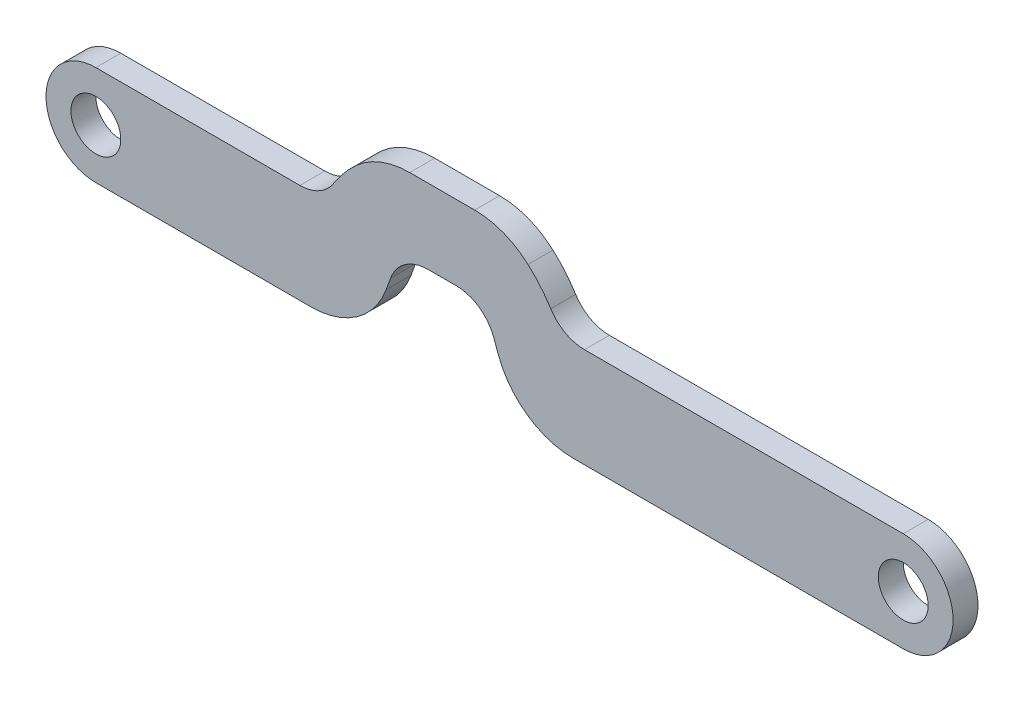
SolidWorks part; units mm, degrees
ref_plane "Спереди" through (0, 0, 0) normal (0, 0, 1) x (1, 0, 0)
ref_plane "Сверху" through (0, 0, 0) normal (0, 1, 0) x (1, 0, 0)
ref_plane "Справа" through (0, 0, 0) normal (1, 0, 0) x (0, 0, -1)
sketch "Эскиз1" plane through (0, 0, 0) normal (0, 0, 1) x (1, 0, 0)
  line L0 (0, 0) -> (-32.398, 0)
  line L1 (-32.398, -2) -> (0, -2)
  line L2 (-32.398, 2) -> (0, 2)
  circle A0 centre (-32.398, 0) radius 1
  circle A1 centre (0, 0) radius 1
  circle A2 centre (-32.398, 0) radius 2
  circle A3 centre (0, 0) radius 2
  dimension "D1" = 32.398
extrude "Бобышка-Вытянуть1" add sketch "Эскиз1" along normal mid plane 1 contours A3 L2 A2 L0 | A3 L0 A2 L1 | A2 A0 | A3 A1 region at (-16.199, 1.0162, 0) region at (-31.0238, -1.3742, 0) region at (-16.199, -1.0162, 0) region at (-1.3742, 1.3742, 0)
sketch "Sketch3" plane through (0, 0, 0) normal (0, 0, 1) x (1, 0, 0)
  line L0 (0, 0) -> (-18.5, 0)
  line L1 (-18.5, -2) -> (-13.3079, -2)
  line L2 (-20.5203, 0.7353) -> (-21.5159, -2)
  line L3 (-16.4797, 0.7353) -> (-15.4841, -2)
  line L4 (-18.5, 0) -> (-18.5, -2)
  line L5 (-18.5, -2) -> (-23.727, -2)
  line L6 (-23.3394, 1.7614) -> (-24.335, -0.9739)
  line L7 (-13.6606, 1.7614) -> (-12.665, -0.9739)
  line L8 (-18.5, 2.15) -> (-18.5, 1.65)
  line L9 (-18.5, 1.65) -> (-16.1863, 1.65)
  line L10 (-18.5, 1.65) -> (-20.9188, 1.65)
  line L11 (-18.5, 5.15) -> (-18.5, 4.65)
  line L12 (-18.5, 4.65) -> (-22.2565, 4.65)
  line L13 (-18.5, 4.65) -> (-15.1428, 4.65)
  circle A0 centre (-18.5, 0) radius 2.15
  circle A1 centre (-18.5, 0) radius 5.15
  dimension "D1" = 4.3
extrude "Extrude1" add sketch "Sketch3" along normal mid plane 1 contours A1 L5 L2 A0 L3 | L0 A0 L5 L4 | L8 A0 L10 | L9 A0 L8 region at (-18.8333, 0.1753, 0) region at (-16.2306, 0.4096, 0) region at (-17.974, 1.8521, 0) region at (-19.026, 1.8521, 0)
extrude "Extrude3" cut sketch "Sketch" against normal mid plane 1 contours L0 A0 L9 L10 L5 L4 | A0 L2 L5 | A0 L1 L3 L0 | L1 A0 L0 L4 | A0 L0 L3 region at (-17.5737, -0.8868, 0) region at (-16.3214, 0.1861, 0) region at (-18.8333, 0.1753, 0) region at (-16.3391, -1.3677, 0) region at (-20.6613, -1.3378, 0)
sketch "Sketch" plane through (0, 0, 0) normal (0, 0, 1) x (1, 0, 0) same geometry as "Sketch3"
fillet "Fillet1" radius 1.6 2 edges at (-17.1216, 1.65, 0) (-19.8784, 1.65, 0)
fillet "Fillet2" radius 1.6 2 edges at (-13.7542, 2, 0) (-23.2458, 2, 0)
fillet "Fillet3" radius 3.2 4 edges at (-15.4841, -2, 0) (-21.5159, -2, 0) (-16.2864, 4.65, 0) (-20.7136, 4.65, 0)
